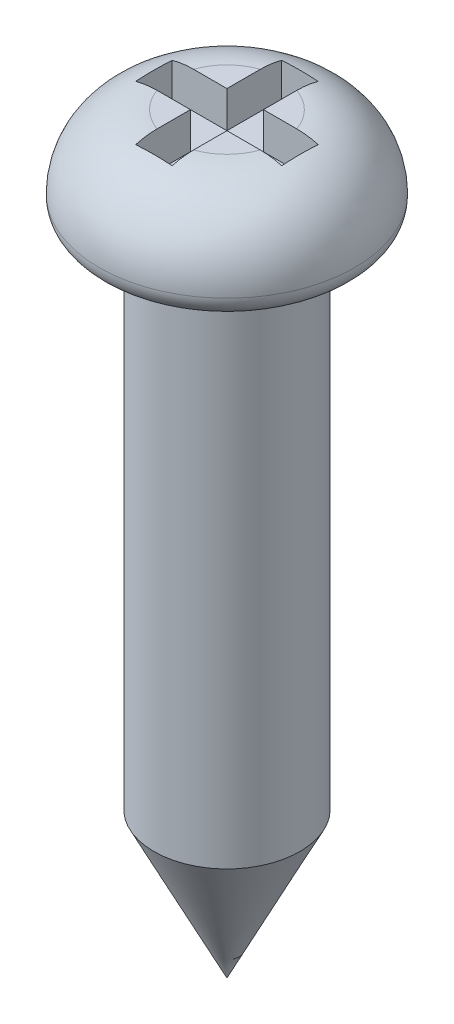
SolidWorks part; units mm, degrees
ref_plane "Front Plane" through (0, 0, 0) normal (0, 0, 1) x (1, 0, 0)
ref_plane "Top Plane" through (0, 0, 0) normal (0, 1, 0) x (1, 0, 0)
ref_plane "Right Plane" through (0, 0, 0) normal (1, 0, 0) x (0, 0, -1)
sketch "Sketch1" plane through (0, 0, 0) normal (0, 1, 0) x (1, 0, 0)
  circle A0 centre (0, 0) radius 2
  dimension "D1" = 4
extrude "Boss-Extrude1" add sketch "Sketch1" along normal blind 18
sketch "Sketch2" plane through (0, 18, 0) normal (0, 1, 0) x (1, 0, 0)
  circle A0 centre (0, 0) radius 3.5
  dimension "D1" = 7
extrude "Boss-Extrude2" add sketch "Sketch2" along normal blind 2.6
sketch "Sketch3" plane through (0, 20.6, 0) normal (0, 1, 0) x (1, 0, 0)
  line L0 (-3.5, 0) -> (3.5, 0) construction
  line L1 (0, 3.5) -> (0, -3.5) construction
  line L2 (-2, -0.5) -> (-2, 0.5)
  line L3 (-2, 0.5) -> (-0.5, 0.5)
  line L4 (-0.5, 0.5) -> (-0.5, 2)
  line L5 (-0.5, 2) -> (0.5, 2)
  line L6 (-0.5, -2) -> (0.5, -2)
  line L7 (-0.5, -0.5) -> (-0.5, -2)
  line L8 (-2, -0.5) -> (-0.5, -0.5)
  line L9 (2, -0.5) -> (0.5, -0.5)
  line L10 (0.5, -0.5) -> (0.5, -2)
  line L11 (0.5, 0.5) -> (0.5, 2)
  line L12 (2, 0.5) -> (0.5, 0.5)
  line L13 (2, -0.5) -> (2, 0.5)
  circle A0 centre (0, 0) radius 3.5 construction
  point P16 (-2, 0)
  point P19 (0, -2)
  point P20 (0, 2)
  point P22 (2, 0)
  dimension "D1" = 0.5
  dimension "D2" = 0.5
  dimension "D3" = 2
  dimension "D4" = 2
extrude "Cut-Extrude1" cut sketch "Sketch3" against normal blind 1
fillet "Fillet1" radius 2 1 edges at (0, 20.6, 3.5)
fillet "Fillet2" radius 0.6 1 edges at (0, 18, 3.5)
chamfer "Chamfer1" distance 2 distance2 4 1 edges at (0, 0, 2) first distance on face at (0, 0, 2)
